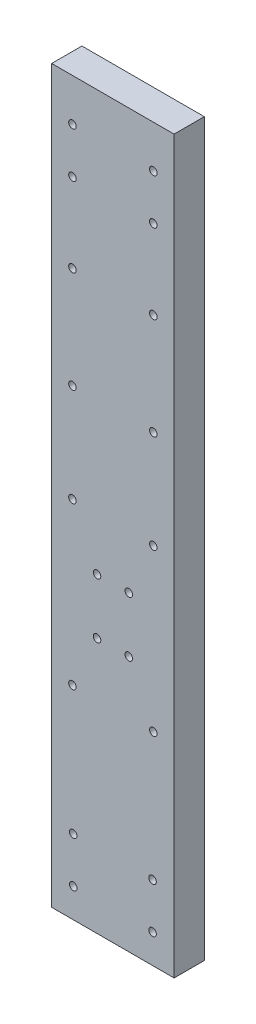
SolidWorks part; units mm, degrees
ref_plane "Front Plane" through (0, 0, 0) normal (0, 0, 1) x (1, 0, 0)
ref_plane "Top Plane" through (0, 0, 0) normal (0, 1, 0) x (1, 0, 0)
ref_plane "Right Plane" through (0, 0, 0) normal (1, 0, 0) x (0, 0, -1)
sketch "Sketch3" plane through (0, 0, 0) normal (0, 0, 1) x (1, 0, 0)
  line L0 (0, 96.73) -> (0, 0)
  line L1 (16.2, 96.73) -> (16.2, 0)
  line L2 (0, 0) -> (16.2, 0)
  line L4 (0, 96.73) -> (16.2, 96.73)
  circle A0 centre (6, 33.85) radius 0.5
  circle A1 centre (10.2, 33.85) radius 0.5
  circle A2 centre (2.75, 85.12) radius 0.5
  circle A3 centre (10.2, 41.17) radius 0.5
  circle A4 centre (13.45, 48.17) radius 0.5
  circle A5 centre (2.75, 91.12) radius 0.5
  circle A6 centre (13.45, 85.12) radius 0.5
  circle A7 centre (2.75, 61.17) radius 0.5
  circle A16 centre (2.85, 9.8464) radius 0.5
  circle A17 centre (13.35, 9.8464) radius 0.5
  circle A18 centre (13.35, 3.8464) radius 0.5
  circle A19 centre (2.85, 3.8464) radius 0.5
  circle A20 centre (13.45, 61.17) radius 0.5
  circle A21 centre (2.75, 74.62) radius 0.5
  circle A22 centre (13.45, 26.85) radius 0.5
  circle A23 centre (13.45, 74.62) radius 0.5
  circle A24 centre (13.45, 91.12) radius 0.5
  circle A25 centre (2.75, 26.85) radius 0.5
  circle A26 centre (6, 41.17) radius 0.5
  circle A27 centre (2.75, 48.17) radius 0.5
extrude "Boss-Extrude3" add sketch "Sketch3" along normal blind 4
